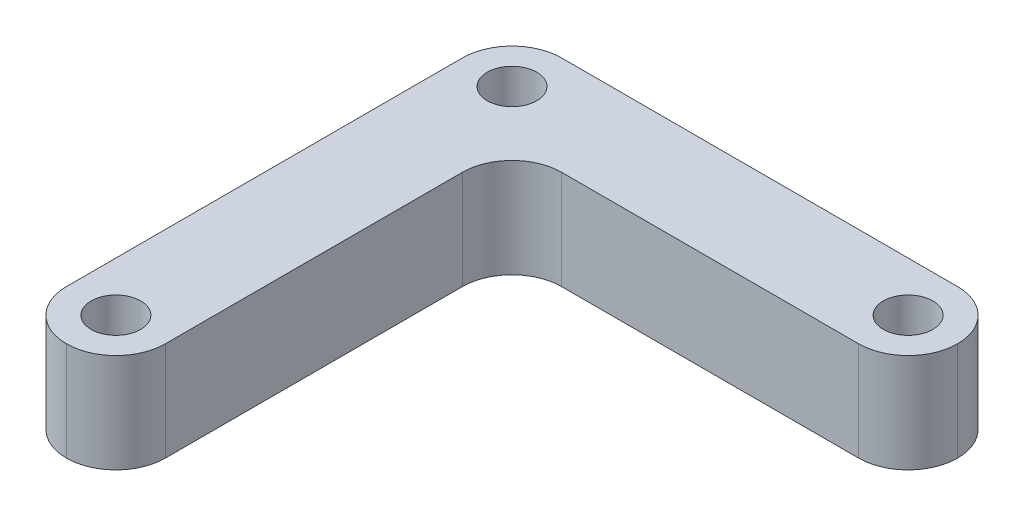
SolidWorks part; units mm, degrees
ref_plane "Front" through (0, 0, 0) normal (0, 0, 1) x (1, 0, 0)
ref_plane "Top" through (0, 0, 0) normal (0, 1, 0) x (1, 0, 0)
ref_plane "Right" through (0, 0, 0) normal (1, 0, 0) x (0, 0, -1)
sketch "Sketch1" plane through (0, 0, 0) normal (0, 1, 0) x (1, 0, 0)
  line L1 (-12.5, -12.5) -> (12.5, -12.5)
  line L2 (-12.5, -12.5) -> (-12.5, 12.5)
  line L3 (-12.5, 12.5) -> (12.5, 12.5)
  line L4 (12.5, -12.5) -> (12.5, 12.5)
  line L5 (-12.5, -12.5) -> (12.5, 12.5) construction
  line L6 (-12.5, 12.5) -> (12.5, -12.5) construction
  point P0 (0, 0)
  dimension "D1" = 25
extrude "Boss-Extrude1" add sketch "Sketch1" along normal blind 5
sketch "Sketch3" plane through (0, 5, 0) normal (0, 1, 0) x (1, 0, 0)
  line L0 (12.5, 12.5) -> (-12.5, 12.5) construction
  line L1 (-12.5, 12.5) -> (-12.5, -12.5) construction
  line L2 (-12.5, -12.5) -> (12.5, -12.5) construction
  line L3 (12.5, -12.5) -> (12.5, 12.5) construction
  circle A0 centre (-10, 10) radius 1.25
  circle A1 centre (10, 10) radius 1.25
  circle A2 centre (-10, -10) radius 1.25
  dimension "D1" = 2.5
  dimension "D2" = 2.5
  dimension "D3" = 2.5
  dimension "D4" = 2.5
  dimension "D5" = 2.5
extrude "Cut-Extrude1" cut sketch "Sketch3" against normal through all
sketch "Sketch4" plane through (0, 5, 0) normal (0, 1, 0) x (1, 0, 0)
  line L5 (-12.5, 12.5) -> (-12.5, -12.5) construction
  line L6 (12.5, -12.5) -> (-7.5, -12.5)
  line L7 (12.5, -12.5) -> (12.5, 7.5)
  line L8 (12.5, 7.5) -> (-7.5, 7.5)
  line L9 (-7.5, -12.5) -> (-7.5, 7.5)
  line L11 (12.5, 12.5) -> (-12.5, 12.5) construction
  dimension "D1" = 5
  dimension "D2" = 5
extrude "Cut-Extrude2" cut sketch "Sketch4" against normal through all
fillet "Fillet1" radius 2.5 6 edges at (-12.5, 2.5, 12.5) (12.5, 2.5, -12.5) (-12.5, 2.5, -12.5) (12.5, 2.5, -7.5) (-7.5, 2.5, 12.5) (-7.5, 2.5, -7.5)
